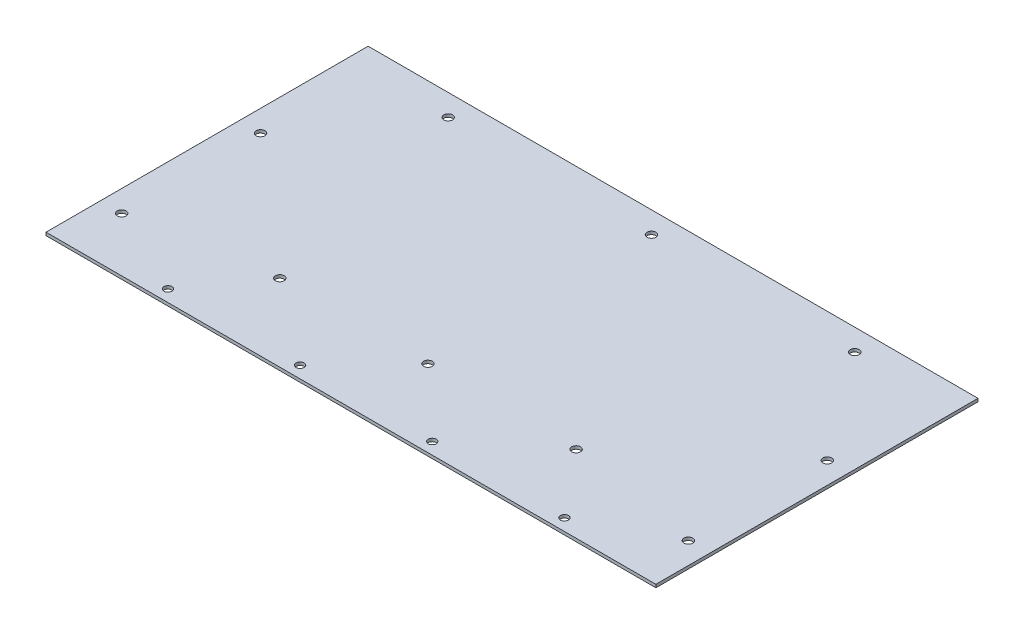
SolidWorks part; units mm, degrees
material "6061-T6 (SS)"
ref_plane "X-Y Datum" through (0, 0, 0) normal (0, 0, 1) x (1, 0, 0)
ref_plane "X-Z Datum" through (0, 0, 0) normal (0, 1, 0) x (1, 0, 0)
ref_plane "Y-Z Datum" through (0, 0, 0) normal (1, 0, 0) x (0, 0, -1)
sketch "Sketch1" plane through (0, 0, 0) normal (0, 0, 1) x (1, 0, 0)
  line L1 (-228.6, -1.143) -> (228.6, -1.143)
  line L2 (-228.6, -1.143) -> (-228.6, 1.143)
  line L3 (-228.6, 1.143) -> (228.6, 1.143)
  line L4 (228.6, -1.143) -> (228.6, 1.143)
  line L5 (-228.6, -1.143) -> (228.6, 1.143) construction
  line L6 (-228.6, 1.143) -> (228.6, -1.143) construction
  point P0 (0, 0)
  dimension "D1" = 2.286
  dimension "D2" = 457.2
extrude "Boss-Extrude1" add sketch "Sketch1" along normal blind 238.3152
sketch "Sketch2" plane through (0, 0, 0) normal (0, 0, -1) x (-1, 0, 0)
  line L22 (-228.6, 1.143) -> (-228.6, -1.143)
  line L23 (-228.6, -1.143) -> (228.6, -1.143)
  line L24 (228.6, -1.143) -> (228.6, 1.143)
  line L25 (228.6, 1.143) -> (-228.6, 1.143)
  line L26 (-228.6, 1.143) -> (-228.6, -1.143)
  line L27 (-228.6, -1.143) -> (228.6, -1.143)
  line L28 (228.6, -1.143) -> (228.6, 1.143)
  line L29 (228.6, 1.143) -> (-228.6, 1.143)
  line M6 (-228.6, -1.143) -> (228.6, -1.143)
  line M8 (228.6, 1.143) -> (-228.6, 1.143)
  dimension "D1" = 0
extrude "Boss-Extrude2" add sketch "Sketch2" along normal blind 3.175 contours M8 M6 | M8 M6 region at (0, 0, 0)
sketch "Sketch9" plane through (0, 1.143, 0) normal (0, 1, 0) x (1, 0, 0)
  line L0 (-146.05, -238.3152) -> (-146.05, -229.4252) construction
  line L1 (228.6, -238.3152) -> (-228.6, -238.3152) construction
  line L2 (-228.6, -238.3152) -> (-228.6, 3.175) construction
  circle A0 centre (-146.05, -229.4252) radius 3
  dimension "D2" = 82.55
  dimension "D3" = 6
  dimension "D1" = 8.89
extrude "Cut-Extrude10" cut sketch "Sketch9" against normal blind 2.54
pattern_linear "LPattern1" count 4 spacing 99.06 along (1, 0, 0) of "Cut-Extrude10"
sketch "Sketch10" plane through (0, -1.143, 0) normal (0, -1, 0) x (1, 0, 0)
  circle A0 centre (151.13, 229.4252) radius 3 construction
  circle A1 centre (52.07, 229.4252) radius 3 construction
  circle A2 centre (-46.99, 229.4252) radius 3 construction
  circle A3 centre (-146.05, 229.4252) radius 3 construction
  circle A4 centre (151.13, 229.4252) radius 3
  circle A5 centre (52.07, 229.4252) radius 3
  circle A6 centre (-46.99, 229.4252) radius 3
  circle A7 centre (-146.05, 229.4252) radius 3
sketch "Sketch12" plane through (0, -1.143, 0) normal (0, -1, 0) x (1, 0, 0)
  point P0 (-212.419, 93.6448)
  point P1 (-152.4, 13.0175)
  point P3 (0, 13.0175)
  point P5 (152.4, 13.0175)
  point P7 (212.419, 93.6448)
  point P9 (212.419, 197.7848)
  point P11 (111.0665, 180.586)
  point P13 (0, 180.586)
  point P15 (-111.0665, 180.586)
  point P17 (-212.419, 197.7848)
hole_wizard "M6 Clearance Hole1" positions "Sketch12" profile "Sketch13" hole size "M6" standard "ANSI Metric" end condition through all
sketch "Sketch13" plane through (-212.419, -1.143, 93.6448) normal (1, 0, 0) x (0, 0, -1)
  line L0 (0, 0) -> (0, 2.286)
  line L1 (0, 2.286) -> (3.3, 2.286)
  line L2 (3.3, 2.286) -> (3.3, 0)
  line L5 (3.3, 0) -> (0, 0)
  line L11 (0, -6.35) -> (0, 107.95) construction
  dimension "Thru Hole Dia." = 6.6
  dimension "Thru Hole Depth" = 2.286
